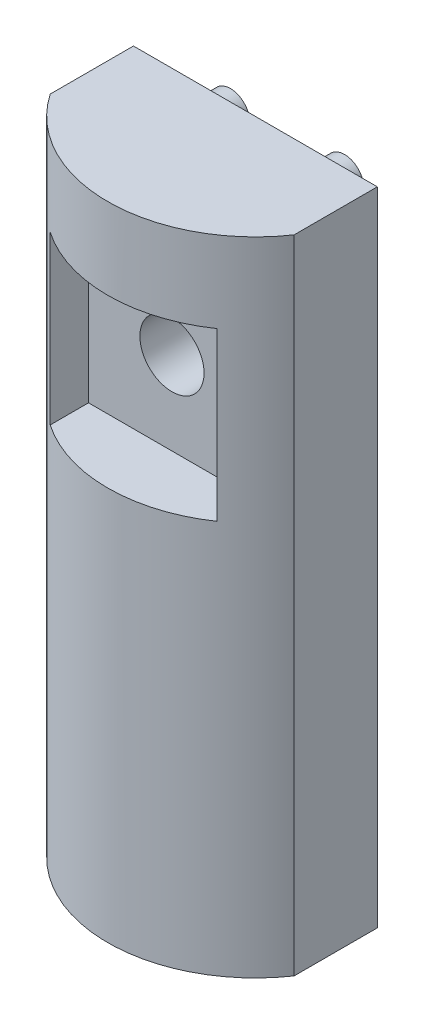
SolidWorks part; units mm, degrees
material "ABS"
ref_plane "Спереди" through (0, 0, 0) normal (0, 0, 1) x (1, 0, 0)
ref_plane "Сверху" through (0, 0, 0) normal (0, 1, 0) x (1, 0, 0)
ref_plane "Справа" through (0, 0, 0) normal (1, 0, 0) x (0, 0, -1)
sketch "Эскиз1" plane through (0, 0, 0) normal (0, 1, 0) x (1, 0, 0)
  line L0 (-23, 0) -> (23, 0)
  arc A0 (-23, 0) -> (23, 0) centre (0, 0) ccw
  dimension "D1" = 23
extrude "Бобышка-Вытянуть1" add sketch "Эскиз1" along normal blind 100
sketch "Эскиз2" plane through (0, 0, 0) normal (0, 0, -1) x (-1, 0, 0)
  line L0 (0, 100) -> (0, 0) construction
  line L1 (-23, 100) -> (23, 100) construction
  line L2 (-23, 50) -> (5.22, 50) construction
  line L3 (-23, 100) -> (-23, 0) construction
  line L4 (-8.89, 93.815) -> (8.89, 93.815) construction
  line L5 (-8.89, 93.815) -> (-8.89, 6.185) construction
  circle A0 centre (-8.89, 93.815) radius 3
  circle A1 centre (8.89, 93.815) radius 3
  circle A2 centre (-8.89, 6.185) radius 3
  circle A3 centre (8.89, 6.185) radius 3
  circle A4 centre (-8.89, 93.815) radius 0.9
  circle A5 centre (8.89, 93.815) radius 0.9
  circle A6 centre (8.89, 6.185) radius 0.9
  circle A7 centre (-8.89, 6.185) radius 0.9
  point P17 (0, 93.815)
  point P19 (-8.89, 50)
  dimension "D1" = 6
  dimension "D4" = 1.8
  dimension "D2" = 2
  dimension "D3" = 2
extrude "Бобышка-Вытянуть2" add sketch "Эскиз2" along normal blind 5
sketch "Эскиз4" plane through (0, 0, 0) normal (0, 0, -1) x (-1, 0, 0)
  line L0 (-23, 0) -> (23, 0) construction
  line L1 (-19, 0) -> (19, 0)
  line L2 (-19, 0) -> (-19, 100)
  line L3 (-19, 100) -> (19, 100)
  line L4 (19, 0) -> (19, 100)
  line L5 (-23, 100) -> (23, 100) construction
  line L7 (-33.2966, 110.6364) -> (33.2966, 110.6364)
  line L8 (-33.2966, 110.6364) -> (-33.2966, -11.5529)
  line L9 (-33.2966, -11.5529) -> (33.2966, -11.5529)
  line L10 (33.2966, 110.6364) -> (33.2966, -11.5529)
  line L11 (-33.2966, 110.6364) -> (33.2966, -11.5529) construction
  line L12 (-33.2966, -11.5529) -> (33.2966, 110.6364) construction
  point P8 (0, 0)
  point P10 (0, 49.5418)
  dimension "D1" = 38
extrude "Вырез-Вытянуть1" cut sketch "Эскиз4" against normal through all
sketch "Эскиз5" plane through (0, 0, 0) normal (0, 0, -1) x (-1, 0, 0)
  line L0 (0, 100) -> (0, 55.9109) construction
  line L1 (-19, 100) -> (19, 100) construction
  line L3 (-13, 87.3507) -> (13, 87.3507)
  line L4 (-13, 87.3507) -> (-13, 61.3507)
  line L5 (-13, 61.3507) -> (13, 61.3507)
  line L6 (13, 87.3507) -> (13, 61.3507)
  point P9 (0, 87.3507)
  dimension "D1" = 26
  dimension "D2" = 26
extrude "Вырез-Вытянуть2" cut sketch "Эскиз5" along normal blind 10 from offset 23 offset against normal yes
sketch "Эскиз6" plane through (0, 0, 13) normal (0, 0, 1) x (1, 0, 0)
  circle A0 centre (0, 74.3507) radius 5
extrude "Вырез-Вытянуть3" cut sketch "Эскиз6" against normal blind 32
